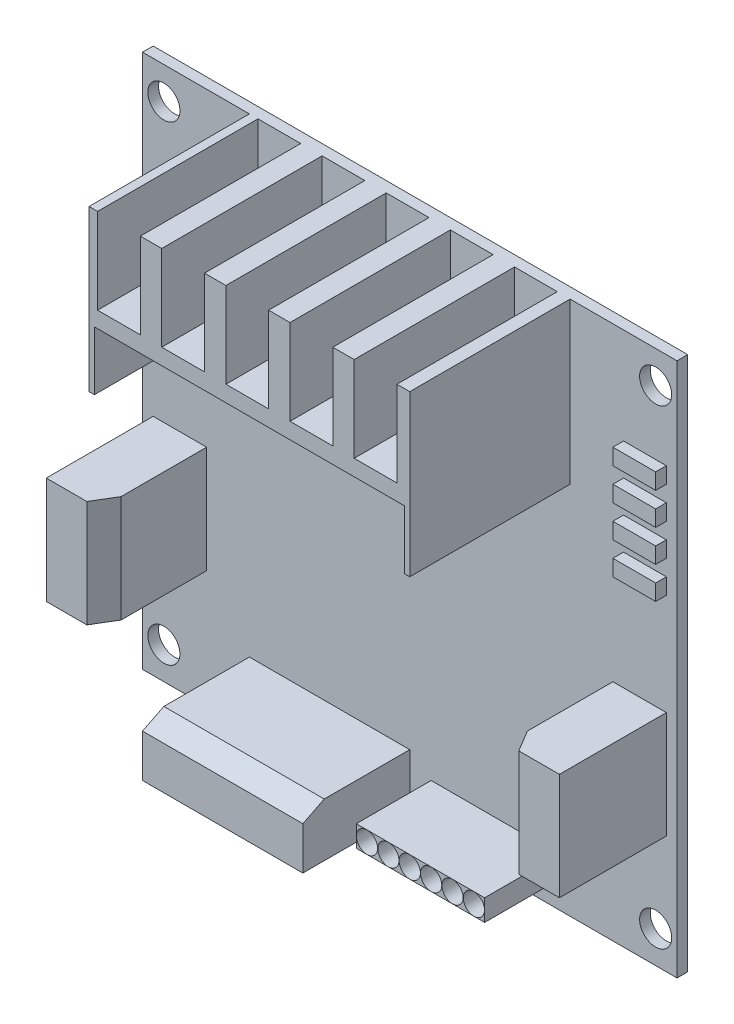
SolidWorks part; units mm, degrees
ref_plane "Front Plane" through (0, 0, 0) normal (0, 0, 1) x (1, 0, 0)
ref_plane "Top Plane" through (0, 0, 0) normal (0, 1, 0) x (1, 0, 0)
ref_plane "Right Plane" through (0, 0, 0) normal (1, 0, 0) x (0, 0, -1)
sketch "Sketch1" plane through (0, 0, 0) normal (0, 0, 1) x (1, 0, 0)
  line L1 (0, 0) -> (50, 0)
  line L2 (0, 0) -> (0, 50)
  line L3 (0, 50) -> (50, 50)
  line L4 (50, 0) -> (50, 50)
  dimension "D1" = 50
  dimension "D2" = 50
extrude "Boss-Extrude1" add sketch "Sketch1" along normal blind 1
sketch "Sketch2" plane through (0, 0, 1) normal (0, 0, 1) x (1, 0, 0)
  line L0 (50, 50) -> (0, 50) construction
  line L1 (10, 50) -> (40, 50)
  line L2 (10, 50) -> (10, 35)
  line L3 (10, 35) -> (40, 35)
  line L4 (40, 50) -> (40, 35)
  line L5 (0, 0) -> (50, 0) construction
  point P6 (25, 35)
  point P9 (25, 0)
  dimension "D1" = 15
  dimension "D2" = 30
extrude "Boss-Extrude2" add sketch "Sketch2" along normal blind 15
sketch "Sketch3" plane through (0, 0, 16) normal (0, 0, 1) x (1, 0, 0)
  line L0 (40, 50) -> (10, 50) construction
  line L1 (10.8, 50) -> (14.8, 50)
  line L2 (10.8, 50) -> (10.8, 42)
  line L3 (10.8, 42) -> (14.8, 42)
  line L4 (14.8, 50) -> (14.8, 42)
  line L5 (10, 50) -> (10, 35) construction
  dimension "D1" = 4
  dimension "D2" = 8
  dimension "D3" = 0.8
extrude "Cut-Extrude1" cut sketch "Sketch3" against normal blind 15 contours L2 L3 L4 L1
pattern_linear "LPattern1" count 5 spacing 6 along (1, 0, 0) of "Cut-Extrude1"
sketch "Sketch4" plane through (0, 0, 16) normal (0, 0, 1) x (1, 0, 0)
  line L1 (10.5021, 35) -> (39.5, 35)
  line L2 (10.5021, 35) -> (10.5021, 40.5)
  line L3 (10.5021, 40.5) -> (39.5, 40.5)
  line L4 (39.5, 35) -> (39.5, 40.5)
  line L5 (16.8, 42) -> (20.8, 42) construction
  line L6 (10.5021, 35) -> (39.5, 35)
  line L7 (10.5021, 35) -> (10.5021, 37)
  line L8 (10.5021, 37) -> (39.5, 37)
  line L9 (39.5, 35) -> (39.5, 37)
  line L10 (10, 35) -> (40, 35) construction
  line L11 (10.5021, 40.5) -> (39.5, 40.5)
  line L12 (10.5021, 40.5) -> (10.5021, 39.5)
  line L13 (10.5021, 39.5) -> (39.5, 39.5)
  line L14 (39.5, 40.5) -> (39.5, 39.5)
  line L15 (40, 35) -> (40, 50) construction
  line L16 (10, 50) -> (10, 35) construction
  line M17 (10, 50) -> (10, 35)
  line M18 (10, 35) -> (40, 35)
  line M19 (40, 35) -> (40, 50)
  dimension "D1" = 1.5
  dimension "D2" = 2
  dimension "D3" = 1
  dimension "D4" = 0.5
  dimension "D5" = 0.5021
extrude "Cut-Extrude2" cut sketch "Sketch4" against normal blind 2 contours L13 L2 L8 L4 | L8 L2 M18 M19 | L13 L3 M17 M19 region at (25.001, 36, 16) region at (25.001, 38.25, 16) region at (25.001, 40, 16)
extrude "Cut-Extrude3" cut sketch "Sketch4<3>" against normal blind 5 from surface contours L13 L2 L8 L4 | L8 L2 M18 M19 region at (25.001, 36, 16) region at (25.001, 38.25, 16) starting at face at (25.001, 37.75, 14)
sketch "Sketch4<3>" plane through (0, 0, 16) normal (0, 0, 1) x (1, 0, 0) same geometry as "Sketch4"
extrude "Cut-Extrude4" cut sketch "Sketch4<4>" against normal up to surface (15 mm away) from surface contours L8 L2 M18 M19 region at (25.001, 36, 16) up to face at (25, 33.75, 1) starting at face at (25.001, 37.25, 9)
sketch "Sketch4<4>" plane through (0, 0, 16) normal (0, 0, 1) x (1, 0, 0) same geometry as "Sketch4"
sketch "Sketch5" plane through (0, 39.5, 0) normal (0, -1, 0) x (1, 0, 0)
  line L0 (12.0021, 14) -> (10.5021, 14)
  line L1 (10.5021, 14) -> (39.5, 14) construction
  line L2 (10.5021, 14) -> (10.5021, 12.5)
  line L3 (10.5021, 9) -> (10.5021, 14) construction
  line L4 (10.5021, 12.5) -> (12.0021, 14)
  line L5 (38, 14) -> (39.5, 14)
  line L6 (39.5, 14) -> (39.5, 12.5)
  line L7 (39.5, 1) -> (39.5, 16) construction
  line L8 (39.5, 12.5) -> (38, 14)
  dimension "D1" = 1.5
  dimension "D2" = 1.5
  dimension "D3" = 1.5
  dimension "D4" = 1.5
extrude "Cut-Extrude5" cut sketch "Sketch5" against normal up to surface (1 mm away) up to face at (25.001, 40.5, 15)
sketch "Sketch6" plane through (0, 39.5, 0) normal (0, -1, 0) x (1, 0, 0)
  line L0 (12.0021, 14) -> (38, 14) construction
  line L4 (24.851, 10.25) -> (25.151, 10.25)
  line L5 (24.851, 10.25) -> (24.851, 12.75)
  line L6 (24.851, 12.75) -> (25.151, 12.75)
  line L7 (25.151, 10.25) -> (25.151, 12.75)
  line L8 (24.851, 10.25) -> (25.151, 12.75) construction
  line L9 (24.851, 12.75) -> (25.151, 10.25) construction
  line L10 (23.751, 11.35) -> (26.251, 11.35)
  line L11 (23.751, 11.35) -> (23.751, 11.65)
  line L12 (23.751, 11.65) -> (26.251, 11.65)
  line L13 (26.251, 11.35) -> (26.251, 11.65)
  line L14 (23.751, 11.35) -> (26.251, 11.65) construction
  line L15 (23.751, 11.65) -> (26.251, 11.35) construction
  circle A0 centre (25.001, 11.5) radius 1.5
  point P5 (25.001, 14)
  dimension "D1" = 3
  dimension "D2" = 2.5
  dimension "D3" = 0.3
  dimension "D4" = 0.3
  dimension "D5" = 2.5
  dimension "D6" = 2.5
extrude "Boss-Extrude3" add sketch "Sketch6" along normal blind 0.1 contours L12 L11 L10 L5 | L12 L5 L10 L7 | L5 L12 L7 L6 | L10 L13 L12 L7 | L10 L5 L4 L7 | A0 L13 L10 L7 L4 L5 L11 L12 L6 region at (25.001, 39.5, 10.8) region at (24.301, 39.5, 11.5) region at (25.001, 39.5, 11.5) region at (25.701, 39.5, 11.5) region at (25.001, 39.5, 12.2) region at (23.5435, 39.5, 11.5)
extrude "Boss-Extrude4" add sketch "Sketch6<3>" along normal blind 1 contours A0 L13 L10 L7 L4 L5 L11 L12 L6 region at (23.5435, 39.5, 11.5)
sketch "Sketch6<3>" plane through (0, 39.5, 0) normal (0, -1, 0) x (1, 0, 0) same geometry as "Sketch6"
sketch "Sketch7" plane through (0, 0, 1) normal (0, 0, 1) x (1, 0, 0)
  line L0 (50, 50) -> (40, 50) construction
  line L1 (50, 0) -> (50, 50) construction
  line L2 (0, 0) -> (50, 0) construction
  line L3 (0, 50) -> (0, 0) construction
  line L4 (10, 50) -> (0, 50) construction
  circle A0 centre (48, 47) radius 1.5
  circle A1 centre (48, 3) radius 1.5
  circle A2 centre (2, 3) radius 1.5
  circle A3 centre (2, 47) radius 1.5
  dimension "D1" = 3
  dimension "D4" = 3
  dimension "D7" = 3
  dimension "D10" = 3
  dimension "D2" = 3
  dimension "D3" = 2
  dimension "D5" = 3
  dimension "D6" = 2
  dimension "D8" = 2
  dimension "D9" = 3
  dimension "D11" = 3
  dimension "D12" = 2
extrude "Cut-Extrude6" cut sketch "Sketch7" against normal through all
sketch "Sketch8" plane through (0, 0, 1) normal (0, 0, 1) x (1, 0, 0)
  line L1 (49, 41) -> (45, 41)
  line L2 (49, 41) -> (49, 39.5)
  line L3 (49, 39.5) -> (45, 39.5)
  line L4 (45, 41) -> (45, 39.5)
  line L5 (50, 0) -> (50, 50) construction
  circle A0 centre (48, 47) radius 1.5 construction
  dimension "D1" = 1.5
  dimension "D2" = 4
  dimension "D3" = 1
  dimension "D4" = 6
extrude "Boss-Extrude5" add sketch "Sketch8" along normal blind 1
pattern_linear "LPattern2" count 4 spacing 3 along (0, -1, 0) of "Boss-Extrude5"
ref_plane "Plane1" through (25, 0, 0) normal (1, 0, 0) x (0, 0, -1)
mirror "Mirror1" about plane through (25, 0, 0) normal (1, 0, 0) of "LPattern2"
sketch "Sketch9" plane through (0, 0, 1) normal (0, 0, 1) x (1, 0, 0)
  line L0 (50, 0) -> (50, 50) construction
  line L1 (49, 11) -> (44, 11)
  line L2 (49, 11) -> (49, 21)
  line L3 (49, 21) -> (44, 21)
  line L4 (44, 11) -> (44, 21)
  circle A0 centre (48, 3) radius 1.5 construction
  dimension "D1" = 5
  dimension "D2" = 10
  dimension "D3" = 1
  dimension "D4" = 8
extrude "Boss-Extrude6" add sketch "Sketch9" along normal blind 10
sketch "Sketch10" plane through (0, 21, 0) normal (0, 1, 0) x (1, 0, 0)
  line L0 (45.2, -11) -> (44, -11)
  line L1 (49, -11) -> (44, -11) construction
  line L2 (44, -11) -> (44, -9)
  line L3 (44, -11) -> (44, -1) construction
  line L4 (44, -9) -> (45.2, -11)
  dimension "D1" = 2
  dimension "D2" = 1.2
extrude "Cut-Extrude7" cut sketch "Sketch10" against normal blind 10
mirror "Mirror2" about plane through (25, 0, 0) normal (1, 0, 0) of "Cut-Extrude7", "Boss-Extrude6"
sketch "Sketch11" plane through (0, 0, 1) normal (0, 0, 1) x (1, 0, 0)
  line L0 (0, 0) -> (50, 0) construction
  line L1 (10, 1) -> (25, 1)
  line L2 (10, 1) -> (10, 6)
  line L3 (10, 6) -> (25, 6)
  line L4 (25, 1) -> (25, 6)
  circle A0 centre (2, 3) radius 1.5 construction
  dimension "D1" = 15
  dimension "D2" = 5
  dimension "D3" = 8
  dimension "D4" = 1
extrude "Boss-Extrude7" add sketch "Sketch11" along normal blind 10
sketch "Sketch12" plane through (25, 0, 0) normal (1, 0, 0) x (0, 0, -1)
  line L0 (-11, 5) -> (-11, 6)
  line L1 (-11, 1) -> (-11, 6) construction
  line L2 (-11, 6) -> (-9, 6)
  line L3 (-9, 6) -> (-11, 5)
  line L4 (-11, 6) -> (-1, 6) construction
  dimension "D1" = 1
  dimension "D2" = 2
extrude "Cut-Extrude8" cut sketch "Sketch12" against normal up to next
sketch "Sketch13" plane through (0, 0, 1) normal (0, 0, 1) x (1, 0, 0)
  line L0 (25, 1) -> (25, 6) construction
  line L1 (27, 2.5) -> (29, 2.5)
  line L2 (27, 2.5) -> (27, 4.5)
  line L3 (27, 4.5) -> (29, 4.5)
  line L4 (29, 2.5) -> (29, 4.5)
  circle A0 centre (28, 3.5) radius 0.995
  point P10 (25, 3.5)
  point P13 (28, 2.5)
  point P14 (29, 3.5)
  dimension "D1" = 1.99
  dimension "D2" = 2
  dimension "D3" = 2
  dimension "D4" = 2
extrude "Boss-Extrude9" add sketch "Sketch13" along normal blind 7
pattern_linear "LPattern3" count 6 spacing 2 along (1, 0, 0) of "Boss-Extrude9"
